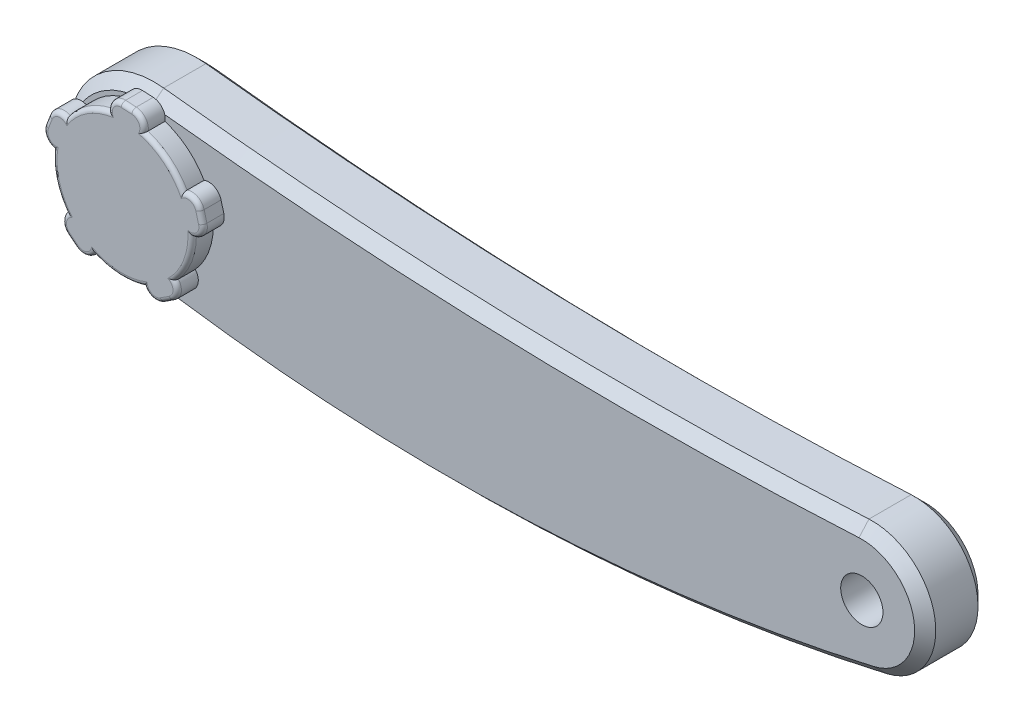
SolidWorks part; units mm, degrees
ref_plane "Front Plane" through (0, 0, 0) normal (0, 0, 1) x (1, 0, 0)
ref_plane "Top Plane" through (0, 0, 0) normal (0, 1, 0) x (1, 0, 0)
ref_plane "Right Plane" through (0, 0, 0) normal (1, 0, 0) x (0, 0, -1)
sketch "Sketch1" plane through (0, 0, 0) normal (0, 0, 1) x (1, 0, 0)
  line L0 (-85, 0) -> (85, 0) construction
  circle A0 centre (-85, 0) radius 20
  circle A1 centre (85, 0) radius 15
  arc A2 (-82.7465, 19.8726) -> (84.1861, 14.9779) centre (29.9265, 1013.5048) ccw
  arc A3 (-88.3618, -19.7154) -> (88.3697, -14.6166) centre (-12.7206, 423.8817) ccw
  point P4 (0, 0)
  dimension "D2" = 40
  dimension "D3" = 30
  dimension "D4" = 450
  dimension "D5" = 1000
  dimension "D1" = 170
extrude "Boss-Extrude1" add sketch "Sketch1" along normal mid plane 15 contours A0 | A0 L0 A1 A2 | L0 A0 A3 A1 | A1 region at (-1.0237, 7.6812, 0) region at (-72.4659, -14.8523, 0) region at (-0.4487, -12.3679, 0) region at (74.4175, 10.0231, 0)
chamfer "Chamfer1" distance 2.5 angle 45 8 edges at (0.2568, -25.9311, -7.5) (-104.8018, 2.8087, -7.5) (99.8523, 2.0996, -7.5) (0.6174, 13.9344, -7.5) (0.2568, -25.9311, 7.5) (-104.8018, 2.8087, 7.5) (99.8523, 2.0996, 7.5) (0.6174, 13.9344, 7.5)
sketch "Sketch2" plane through (0, 0, 7.5) normal (0, 0, 1) x (1, 0, 0)
  circle A0 centre (-85, 0) radius 16.5
  dimension "D1" = 33
extrude "Boss-Extrude2" add sketch "Sketch2" along normal blind 5
sketch "Sketch3" plane through (0, 0, 12.5) normal (0, 0, 1) x (1, 0, 0)
  line L3 (-85, 0) -> (-68.9097, 0)
  line L8 (-66.0119, 3.7765) -> (-66.6676, 6.2235)
  line L9 (-71.0654, 8.0452) -> (-85, 0)
  line L10 (-85, 0) -> (-66.3397, 5) construction
  line L11 (-73.0426, -10.7665) -> (-85, 0)
  line L12 (-75.5407, -16.8918) -> (-73.416, -15.512)
  line L13 (-85, 0) -> (-80.0278, -15.3028)
  line L14 (-91.5445, -14.6992) -> (-85, 0)
  line L15 (-98.142, -14.2161) -> (-96.1731, -15.8105)
  line L16 (-85, 0) -> (-98.0173, -9.4577)
  line L17 (-101.0022, 1.6819) -> (-85, 0)
  line L18 (-102.5814, 8.1057) -> (-103.4893, 5.7406)
  line L19 (-85, 0) -> (-98.0173, 9.4577)
  line L20 (-88.3454, 15.7387) -> (-85, 0)
  line L21 (-82.724, 19.2257) -> (-85.2539, 19.3583)
  line L22 (-85, 0) -> (-80.0278, 15.3028)
  arc A2 (-73.416, -15.512) -> (-73.0426, -10.7665) centre (-75.05, -12.996) ccw
  arc A3 (-68.9097, 0) -> (-66.0119, 3.7765) centre (-68.9097, 3) ccw
  arc A4 (-66.6676, 6.2235) -> (-71.0654, 8.0452) centre (-69.5654, 5.4471) ccw
  arc A5 (-80.0278, -15.3028) -> (-75.5407, -16.8918) centre (-77.1746, -14.3758) ccw
  arc A6 (-96.1731, -15.8105) -> (-91.5445, -14.6992) centre (-94.2852, -13.479) ccw
  arc A7 (-98.0173, -9.4577) -> (-98.142, -14.2161) centre (-96.254, -11.8847) ccw
  arc A8 (-103.4893, 5.7406) -> (-101.0022, 1.6819) centre (-100.6886, 4.6655) ccw
  arc A9 (-98.0173, 9.4577) -> (-102.5814, 8.1057) centre (-99.7807, 7.0306) ccw
  arc A10 (-85.2539, 19.3583) -> (-88.3454, 15.7387) centre (-85.4109, 16.3624) ccw
  arc A11 (-80.0278, 15.3028) -> (-82.724, 19.2257) centre (-82.881, 16.2299) ccw
  circle A14 centre (-85, 0) radius 16.5 construction
  circle A15 centre (-85, 0) radius 2
  point P12 (-67.6795, 10)
  point P44 (-85, 0)
  circle M4 centre (-85, 0) radius 16.5
  dimension "D3" = 3
  dimension "D5" = 4
  dimension "D1" = 30
  dimension "D2" = 20
  dimension "D4" = 5
extrude "Boss-Extrude3" add sketch "Sketch3" against normal blind 5 contours A15 L22 A11 A10 L20 M4 | A11 L21 A10 M4 | L10 L8 A4 M4 | L10 A3 L8 M4 | A15 L10 A4 L9 M4 | L10 A15 L3 A3 M4 | A15 L13 A5 A2 L11 M4 | A15 L16 A7 A6 L14 M4 | A15 L19 A9 A8 L17 M4 | A9 L18 A8 M4 | A7 L15 A6 M4 | A5 L12 A2 M4 | A15 region at (-73.9833, 1.4506, 12.5) region at (-74.734, 4.2521, 12.5) region at (-78.9998, -9.2394, 12.5) region at (-91.9331, -8.5616, 12.5) region at (-95.285, 3.9481, 12.5) region at (-84.4234, 11.0017, 12.5) region at (-68.4431, 6.4563, 12.5) region at (-67.4332, 2.6871, 12.5) region at (-75.3796, -14.8141, 12.5) region at (-96.1162, -13.7273, 12.5) region at (-101.4905, 6.3301, 12.5) region at (-84.0756, 17.6395, 12.5)
fillet "Fillet2" radius 1 20 edges at (-100.8276, 9.842, 12.5) (-103.3478, 3.2767, 12.5) (-87.5535, 18.4623, 12.5) (-68.2303, 8.1337, 12.5) (-66.3397, 5, 12.5) (-72.0823, -13.4355, 12.5) (-99.2513, -12.0116, 12.5) (-93.7861, -16.4372, 12.5) (-85.8635, -16.4774, 12.5) (-100.9378, -4.2705, 12.5) (-103.0354, 6.9231, 12.5) (-93.9865, 13.8381, 12.5) (-83.9889, 19.292, 12.5) (-80.5307, 18.0943, 12.5) (-74.6162, 12.8229, 12.5) (-66.4102, 1.3409, 12.5) (-69.5959, -5.9131, 12.5) (-74.4784, -16.2019, 12.5) (-77.9802, -17.2656, 12.5) (-97.1575, -15.0133, 12.5)
sketch "Sketch4" plane through (0, 0, 7.5) normal (0, 0, 1) x (1, 0, 0)
  circle A0 centre (85, 0) radius 5
  dimension "D1" = 10
extrude "Cut-Extrude1" cut sketch "Sketch4" against normal blind 10 contours A0
sketch "Sketch5" plane through (0, 0, -7.5) normal (0, 0, -1) x (-1, 0, 0)
  circle A0 centre (85, 0) radius 5
  dimension "D1" = 10
extrude "Boss-Extrude4" add sketch "Sketch5" along normal blind 10
